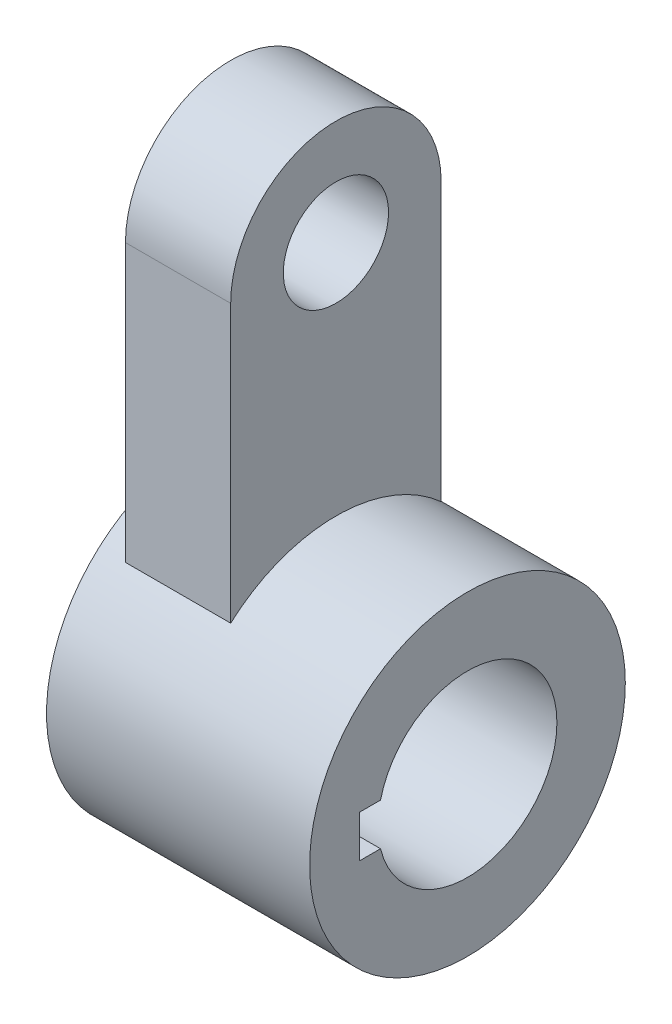
SolidWorks part; units mm, degrees
ref_plane "Front Plane" through (0, 0, 0) normal (1, 0, 0) x (0, 1, 0)
ref_plane "Top Plane" through (0, 0, 0) normal (0, 0, 1) x (0, 1, 0)
ref_plane "Right Plane" through (0, 0, 0) normal (0, 1, 0) x (-1, 0, 0)
sketch "Sketch1" plane through (0, 0, 0) normal (1, 0, 0) x (0, 1, 0)
  line L0 (75, 20) -> (22.3607, 20)
  line L1 (75, -20) -> (22.3607, -20)
  circle A0 centre (0, 0) radius 30
  circle A1 centre (75, 0) radius 10
  arc A2 (75, -20) -> (75, 20) centre (75, 0) ccw
  dimension "D1" = 60
  dimension "D2" = 20
  dimension "D3" = 40
  dimension "D4" = 75
extrude "Boss-Extrude2" add sketch "Sketch1" along normal mid plane 50 contours A0 region at (0, 0, 0)
extrude "Boss-Extrude3" add sketch "Sketch1<3>" against normal blind 20 contours L1 A2 L0 A0 A1 region at (0, 57.0367, 0)
sketch "Sketch1<3>" plane through (0, 0, 0) normal (1, 0, 0) x (0, 1, 0) same geometry as "Sketch1"
sketch "Sketch3" plane through (25, 0, 0) normal (1, 0, 0) x (0, 1, 0)
  line L0 (-4, 20.5227) -> (4, 20.5227)
  line L1 (4, 20.5227) -> (4, 16.5227)
  line L2 (-4, 20.5227) -> (-4, 16.5227)
  arc A0 (-4, 16.5227) -> (4, 16.5227) centre (0, 0) ccw
  point P6 (0, 20.5227)
  dimension "D1" = 34
  dimension "D2" = 8
  dimension "D3" = 4
extrude "Cut-Extrude2" cut sketch "Sketch3" against normal through all
